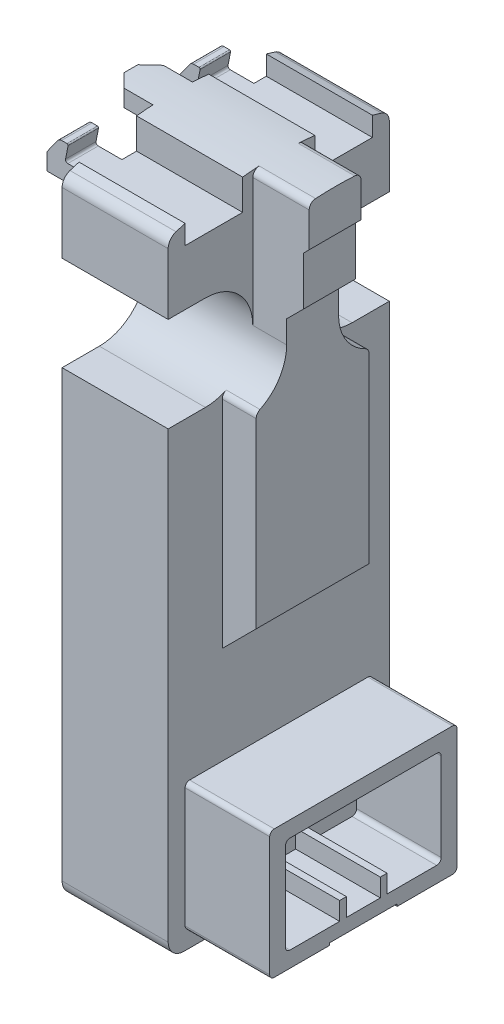
SolidWorks part; units mm, degrees
ref_plane "Front Plane" through (0, 0, 0) normal (0, 0, 1) x (1, 0, 0)
ref_plane "Top Plane" through (0, 0, 0) normal (0, 1, 0) x (1, 0, 0)
ref_plane "Right Plane" through (0, 0, 0) normal (1, 0, 0) x (0, 0, -1)
sketch "Sketch1" plane through (0, 0, 0) normal (1, 0, 0) x (0, 0, -1)
  line L0 (-4.2, 0) -> (4.2, 0)
  line L1 (4.9, 0.7) -> (4.9, 27.3163)
  line L2 (-4.9, 27.3163) -> (-4.9, 0.7)
  arc A0 (-4.9, 0.7) -> (-4.2, 0) centre (-4.2, 0.7) ccw
  arc A1 (4.2, 0) -> (4.9, 0.7) centre (4.2, 0.7) ccw
  arc A2 (4.9, 27.3163) -> (4.5517, 27.7927) centre (4.4, 27.3163) ccw
  arc A3 (4.5517, 27.7927) -> (-4.5517, 27.7927) centre (0, 13.5) ccw
  arc A4 (-4.5517, 27.7927) -> (-4.9, 27.3163) centre (-4.4, 27.3163) ccw
extrude "Boss-Extrude1" add sketch "Sketch1" along normal blind 8.45
ref_plane "Plane1" through (4.7, 0, 0) normal (1, 0, 0) x (0, 0, -1)
sketch "Sketch2" plane through (4.7, 0, 0) normal (1, 0, 0) x (0, 0, -1)
  line L0 (-6, 29) -> (-6, -1)
  line L1 (-6, -1) -> (6, -1)
  line L2 (6, -1) -> (6, 29)
  line L3 (6, 29) -> (-6, 29)
  line L4 (-4.15, 6.25) -> (-4.15, 0.95)
  line L5 (-3.95, 0.75) -> (3.95, 0.75)
  line L6 (4.15, 0.95) -> (4.15, 6.25)
  line L7 (3.95, 6.45) -> (-3.95, 6.45)
  arc A0 (-4.15, 0.95) -> (-3.95, 0.75) centre (-3.95, 0.95) ccw
  arc A1 (3.95, 0.75) -> (4.15, 0.95) centre (3.95, 0.95) ccw
  arc A2 (4.15, 6.25) -> (3.95, 6.45) centre (3.95, 6.25) ccw
  arc A3 (-3.95, 6.45) -> (-4.15, 6.25) centre (-3.95, 6.25) ccw
extrude "Cut-Extrude1" cut sketch "Sketch2" along normal blind 8.45
sketch "Sketch3" plane through (4.7, 0, 0) normal (1, 0, 0) x (0, 0, -1)
  line L0 (-3.45, 5.55) -> (-3.45, 1.65)
  line L1 (-3.25, 1.45) -> (-1.05, 1.45)
  line L2 (-1.05, 1.45) -> (-1.05, 2.25)
  line L3 (-1.05, 2.25) -> (-0.75, 2.25)
  line L4 (-0.75, 2.25) -> (-0.75, 1.45)
  line L5 (-0.75, 1.45) -> (0.75, 1.45)
  line L6 (0.75, 1.45) -> (0.75, 2.25)
  line L7 (0.75, 2.25) -> (1.05, 2.25)
  line L8 (1.05, 2.25) -> (1.05, 1.45)
  line L9 (1.05, 1.45) -> (3.25, 1.45)
  line L10 (3.45, 1.65) -> (3.45, 5.55)
  line L11 (3.25, 5.75) -> (-3.25, 5.75)
  arc A0 (-3.45, 1.65) -> (-3.25, 1.45) centre (-3.25, 1.65) ccw
  arc A1 (3.25, 1.45) -> (3.45, 1.65) centre (3.25, 1.65) ccw
  arc A2 (3.45, 5.55) -> (3.25, 5.75) centre (3.25, 5.55) ccw
  arc A3 (-3.25, 5.75) -> (-3.45, 5.55) centre (-3.25, 5.55) ccw
extrude "Cut-Extrude2" cut sketch "Sketch3" along normal blind 8.45
sketch "Sketch4" plane through (4.7, 0, 0) normal (1, 0, 0) x (0, 0, -1)
  line L0 (1.6, 5.05) -> (1.6, 3.15)
  line L1 (1.6, 3.15) -> (2.4, 3.15)
  line L2 (2.4, 3.15) -> (2.4, 5.05)
  line L3 (2.4, 5.05) -> (1.6, 5.05)
extrude "Cut-Extrude3" cut sketch "Sketch4" against normal blind 8.45
sketch "Sketch5" plane through (4.7, 0, 0) normal (1, 0, 0) x (0, 0, -1)
  line L0 (-2.4, 5.05) -> (-2.4, 3.15)
  line L1 (-2.4, 3.15) -> (-1.6, 3.15)
  line L2 (-1.6, 3.15) -> (-1.6, 5.05)
  line L3 (-1.6, 5.05) -> (-2.4, 5.05)
extrude "Cut-Extrude4" cut sketch "Sketch5" against normal blind 8.45
sketch "Sketch6" plane through (4.7, 0, 0) normal (1, 0, 0) x (0, 0, -1)
  line L0 (-2.5, 20.3419) -> (-2.5, 10.775)
  line L1 (-2.5, 10.775) -> (2.5, 10.775)
  line L2 (2.5, 10.775) -> (2.5, 20.3419)
  line L3 (1.15, 22.5) -> (1.15, 28.1754)
  line L4 (-1.15, 28.1754) -> (-1.15, 22.5)
  arc A0 (2.5, 20.3419) -> (2.3312, 20.6116) centre (2.2, 20.3419) ccw
  arc A1 (2.3312, 20.6116) -> (1.15, 22.5) centre (3.25, 22.5) cw
  arc A2 (1.15, 28.1754) -> (0.8673, 28.4749) centre (0.85, 28.1754) ccw
  arc A3 (0.8673, 28.4749) -> (-0.8673, 28.4749) centre (0, 13.5) ccw
  arc A4 (-0.8673, 28.4749) -> (-1.15, 28.1754) centre (-0.85, 28.1754) ccw
  arc A5 (-1.15, 22.5) -> (-2.3312, 20.6116) centre (-3.25, 22.5) cw
  arc A6 (-2.3312, 20.6116) -> (-2.5, 20.3419) centre (-2.2, 20.3419) ccw
extrude "Boss-Extrude2" add sketch "Sketch6" along normal blind 2.5
sketch "Sketch7" plane through (0, 0, 0) normal (0, 0, 1) x (1, 0, 0)
  line L0 (4.7, 10.775) -> (12.2, 10.775)
  line L1 (12.2, 10.775) -> (12.2, 30.775)
  line L2 (12.2, 30.775) -> (7.2, 30.775)
  line L3 (7.2, 30.775) -> (7.2, 26.65)
  line L4 (7.2, 26.65) -> (6.95, 26.4)
  line L5 (6.95, 26.4) -> (6.95, 24.25)
  line L6 (6.95, 24.25) -> (6.2, 23.5)
  line L7 (6.2, 23.5) -> (6.2, 12.275)
  line L8 (6.2, 12.275) -> (4.7, 10.775)
extrude "Cut-Extrude5" cut sketch "Sketch7" along normal blind 3 and the other way blind 3
sketch "Sketch8" plane through (4.7, 0, 0) normal (1, 0, 0) x (0, 0, -1)
  line L0 (-7, 20.4) -> (-3.25, 20.4)
  line L1 (-3.25, 24.6) -> (-6, 24.6)
  line L2 (-6, 24.6) -> (-6, 30.06)
  line L3 (-6, 30.06) -> (-4.15, 30.06)
  line L4 (-4.15, 30.06) -> (-4.15, 27.06)
  line L5 (-4.15, 27.06) -> (-1.6, 27.06)
  line L6 (-1.6, 27.06) -> (-1.6, 29.06)
  line L7 (-1.6, 29.06) -> (1.6, 29.06)
  line L8 (1.6, 29.06) -> (1.6, 27.06)
  line L9 (1.6, 27.06) -> (4.15, 27.06)
  line L10 (4.15, 27.06) -> (4.15, 30.06)
  line L11 (4.15, 30.06) -> (6, 30.06)
  line L12 (6, 30.06) -> (6, 24.6)
  line L13 (6, 24.6) -> (3.25, 24.6)
  line L14 (3.25, 20.4) -> (7, 20.4)
  line L15 (7, 20.4) -> (7, 31.06)
  line L16 (7, 31.06) -> (-7, 31.06)
  line L17 (-7, 31.06) -> (-7, 20.4)
  arc A0 (-3.25, 20.4) -> (-3.25, 24.6) centre (-3.25, 22.5) ccw
  arc A1 (3.25, 24.6) -> (3.25, 20.4) centre (3.25, 22.5) ccw
extrude "Cut-Extrude6" cut sketch "Sketch8" along normal blind 5 and the other way blind 5
sketch "Sketch9" plane through (0, 0, 0) normal (1, 0, 0) x (0, 0, -1)
  line L0 (-4.15, 19.25) -> (-4.15, 0.75)
  line L1 (-4.15, 0.75) -> (4.15, 0.75)
  line L2 (4.15, 0.75) -> (4.15, 19.25)
  line L3 (4.15, 19.25) -> (-4.15, 19.25)
extrude "Cut-Extrude7" cut sketch "Sketch9" along normal blind 3
sketch "Sketch10" plane through (0, 0, 0) normal (0, 0, 1) x (1, 0, 0)
  line L0 (-1.97, 27.06) -> (-1.97, 26.31)
  line L1 (-1.97, 26.31) -> (0, 26.31)
  line L2 (0, 26.31) -> (0, 27.06)
  line L3 (0, 27.06) -> (-1.0487, 27.06)
  line L4 (-1.1469, 27.1791) -> (-1.0358, 27.7505)
  line L5 (-1.0849, 27.81) -> (-1.3232, 27.81)
  line L6 (-1.485, 27.7276) -> (-1.97, 27.06)
  arc A0 (-1.0487, 27.06) -> (-1.1469, 27.1791) centre (-1.0487, 27.16) cw
  arc A1 (-1.0358, 27.7505) -> (-1.0849, 27.81) centre (-1.0849, 27.76) ccw
  arc A2 (-1.3232, 27.81) -> (-1.485, 27.7276) centre (-1.3232, 27.61) ccw
extrude "Boss-Extrude3" add sketch "Sketch10" against normal blind 3.6 and the other way blind 3.6
sketch "Sketch11" plane through (0, 0, 0) normal (0, 1, 0) x (1, 0, 0)
  line L0 (-3, -2.25) -> (0, -2.25)
  line L1 (0, -2.25) -> (0, 2.25)
  line L2 (0, 2.25) -> (-3, 2.25)
  line L3 (-3, 2.25) -> (-3, -2.25)
extrude "Cut-Extrude8" cut sketch "Sketch11" along normal blind 30
sketch "Sketch12" plane through (0, 0, 0) normal (1, 0, 0) x (0, 0, -1)
  line L0 (-0.875, 28.4745) -> (-0.875, 27.7231)
  line L1 (0.875, 27.7231) -> (0.875, 28.4745)
  arc A0 (-0.875, 27.7231) -> (0.875, 27.7231) centre (0, 13.5) cw
  arc A1 (0.875, 28.4745) -> (-0.875, 28.4745) centre (0, 13.5) ccw
extrude "Boss-Extrude4" add sketch "Sketch12" against normal blind 1.85
sketch "Sketch13" plane through (0, 0, 0) normal (0, 1, 0) x (1, 0, 0)
  line L0 (-3.85, -0.875) -> (-1.2843, -0.875)
  line L1 (-1.2843, -0.875) -> (-1.85, -0.3093)
  line L2 (-1.85, -0.3093) -> (-1.85, 0.3093)
  line L3 (-1.85, 0.3093) -> (-1.2843, 0.875)
  line L4 (-1.2843, 0.875) -> (-3.85, 0.875)
  line L5 (-3.85, 0.875) -> (-3.85, -0.875)
extrude "Cut-Extrude9" cut sketch "Sketch13" along normal blind 30
sketch "Sketch14" plane through (0, 0, 0) normal (0, 1, 0) x (1, 0, 0)
  line L0 (1.1, 1.2) -> (1.1, -1.2)
  line L1 (1.4, -1.5) -> (9.1, -1.5)
  line L2 (9.1, -1.5) -> (9.1, 1.5)
  line L3 (9.1, 1.5) -> (1.4, 1.5)
  arc A0 (1.1, -1.2) -> (1.4, -1.5) centre (1.4, -1.2) ccw
  arc A1 (1.4, 1.5) -> (1.1, 1.2) centre (1.4, 1.2) ccw
extrude "Cut-Extrude10" cut sketch "Sketch14" along normal blind 0.85
ref_plane "Plane2" through (0, 0.2, 0) normal (0, 1, 0) x (1, 0, 0)
ref_plane "Plane3" through (6.246, 0, 0) normal (1, 0, 0) x (0, 0, -1)
ref_plane "NEBV XY" through (6.246, 0, 0) normal (1, 0, 0) x (0, 0, -1)
ref_plane "NEBV XZ" through (0, 4.1, 0) normal (0, 1, 0) x (1, 0, 0)
ref_plane "NEBV YZ" through (0, 0, 0) normal (0, 0, 1) x (1, 0, 0)
ref_axis "NEBV X" through (6.246, 4.1, -80.9) along (0, 0, 1)
ref_axis "NEBV Y" through (6.246, 50, 0) along (0, -1, 0)
ref_axis "NEBV Z" through (80.9, 4.1, 0) along (-1, 0, 0)
sketch3d "NEBV"
  point P0 (6.246, 4.1, 0)
ref_plane "VAVE XY" through (0, 0.2, 0) normal (0, -1, 0) x (-1, 0, 0)
ref_plane "VAVE XZ" through (0, 0, 0) normal (0, 0, -1) x (-1, 0, 0)
ref_plane "VAVE YZ" through (0.92, 0, 0) normal (1, 0, 0) x (0, 0, -1)
ref_axis "VAVE X" through (-80.9, 0.2, 0) along (1, 0, 0)
ref_axis "VAVE Y" through (0.92, 0.2, -50) along (0, 0, 1)
ref_axis "VAVE Z" through (0.92, -50, 0) along (0, 1, 0)
sketch3d "VAVE"
  point P0 (0.92, 0.2, 0)
